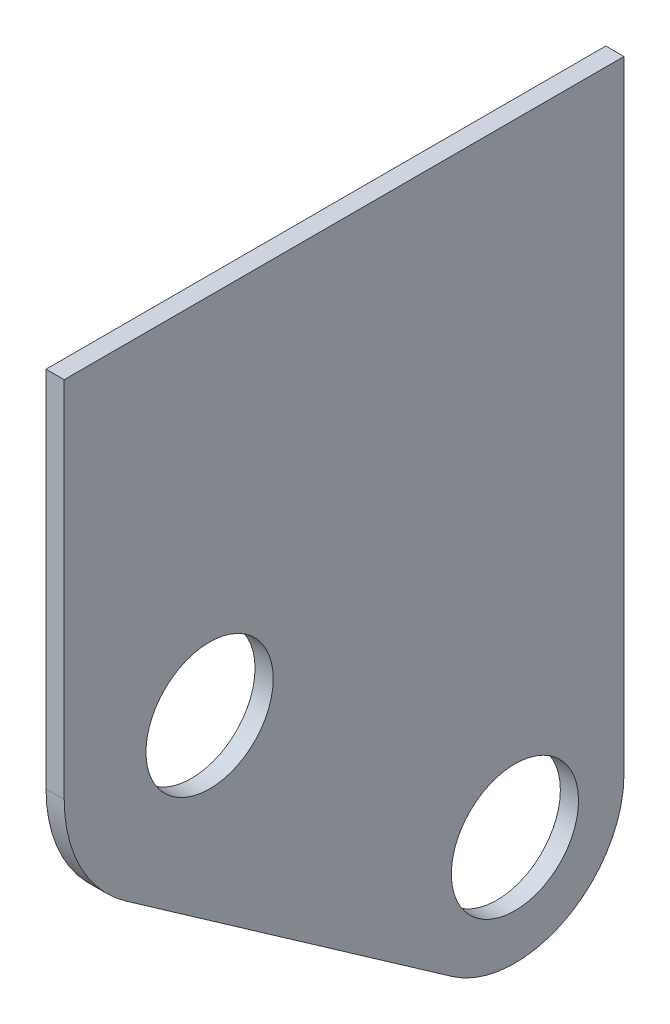
SolidWorks part; units mm, degrees
ref_plane "Front" through (0, 0, 0) normal (0, 0, 1) x (1, 0, 0)
ref_plane "Top" through (0, 0, 0) normal (0, 1, 0) x (1, 0, 0)
ref_plane "Right" through (0, 0, 0) normal (1, 0, 0) x (0, 0, -1)
sketch "Sketch2" plane through (0, 0, 0) normal (1, 0, 0) x (0, 0, -1)
  line L0 (48.8943, 0) -> (-48.8943, 0)
  line L1 (-48.8943, 0) -> (-48.8943, -63.5)
  line L2 (-38.0632, -84.3065) -> (18.9177, -124.2049)
  line L3 (48.8943, -108.6) -> (48.8943, 0)
  circle A0 centre (-23.4943, -63.5) radius 11.1125
  circle A1 centre (29.8443, -108.6) radius 11.1125
  circle A2 centre (-23.4943, -63.5) radius 19.05 construction
  circle A3 centre (29.8443, -108.6) radius 12.7 construction
  arc A4 (-48.8943, -63.5) -> (-38.0632, -84.3065) centre (-23.4943, -63.5) ccw
  arc A5 (18.9177, -124.2049) -> (48.8943, -108.6) centre (29.8443, -108.6) ccw
  point P0 (-29.5985, -50.606)
  point P4 (0, 0)
  point P7 (0, 0)
  point P17 (30.9139, -175.6556)
  point P18 (0, 0)
  dimension "D1" = 22.225
  dimension "D2" = 38.1
  dimension "D3" = 25.4
  dimension "D4" = 38.1
  dimension "D5" = 6.35
  dimension "D6" = 6.35
  dimension "D7" = 125
  dimension "D8" = 63.5
extrude "Boss-Extrude1" add sketch "Sketch2" along normal blind 3.175
